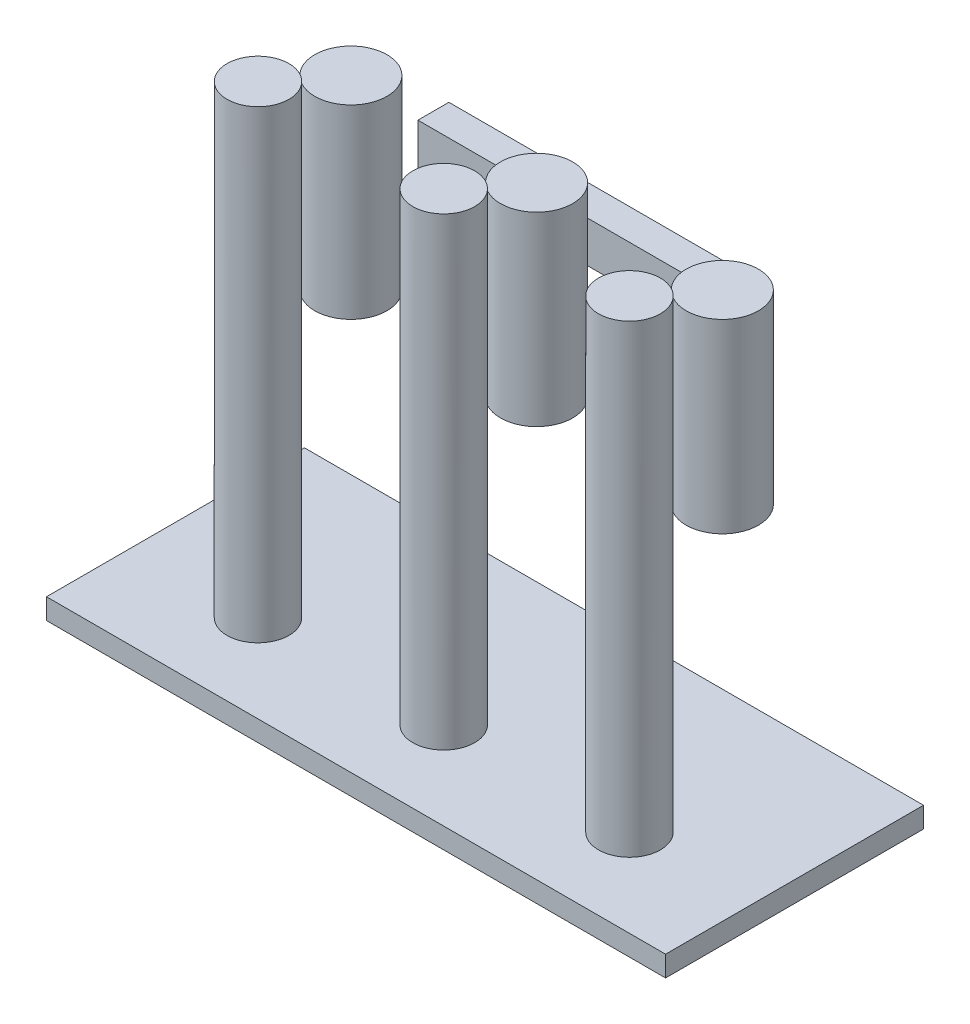
SolidWorks part; units mm, degrees
ref_plane "Front Plane" through (0, 0, 0) normal (0, 0, 1) x (1, 0, 0)
ref_plane "Top Plane" through (0, 0, 0) normal (0, 1, 0) x (1, 0, 0)
ref_plane "Right Plane" through (0, 0, 0) normal (1, 0, 0) x (0, 0, -1)
other "Configuration Table"
sketch "Sketch1" plane through (0, 0, 0) normal (0, 1, 0) x (1, 0, 0)
  line L1 (-3000, -1250) -> (3000, -1250)
  line L2 (-3000, -1250) -> (-3000, 1250)
  line L3 (-3000, 1250) -> (3000, 1250)
  line L4 (3000, -1250) -> (3000, 1250)
extrude "Boss-Extrude1" add sketch "Sketch1" along normal blind 200
sketch "Sketch2" plane through (0, 0, 0) normal (0, 1, 0) x (1, 0, 0)
  circle A0 centre (-1800, -400) radius 300
extrude "Boss-Extrude2" add sketch "Sketch2" along normal blind 4500 from offset 200
sketch "Sketch3" plane through (0, 0, 0) normal (0, 1, 0) x (1, 0, 0)
  circle A0 centre (-1800, 500) radius 350
extrude "Boss-Extrude3" add sketch "Sketch3" along normal blind 1800 from offset 2500
sketch "Sketch4" plane through (0, 0, 0) normal (0, 1, 0) x (1, 0, 0)
  circle A0 centre (0, -400) radius 300
extrude "Boss-Extrude4" add sketch "Sketch4" along normal blind 4500 from offset 200
sketch "Sketch5" plane through (0, 0, 0) normal (0, 1, 0) x (1, 0, 0)
  circle A0 centre (0, 500) radius 350
extrude "Boss-Extrude5" add sketch "Sketch5" along normal blind 1800 from offset 2500
sketch "Sketch6" plane through (0, 0, 0) normal (0, 1, 0) x (1, 0, 0)
  circle A0 centre (1800, -400) radius 300
extrude "Boss-Extrude6" add sketch "Sketch6" along normal blind 4500 from offset 200
sketch "Sketch7" plane through (0, 0, 0) normal (0, 1, 0) x (1, 0, 0)
  circle A0 centre (1800, 500) radius 350
extrude "Boss-Extrude7" add sketch "Sketch7" along normal blind 1800 from offset 2500
sketch "Sketch8" plane through (0, 0, 0) normal (0, 1, 0) x (1, 0, 0)
  line L1 (-1500, 850) -> (1500, 850)
  line L2 (-1500, 850) -> (-1500, 1150)
  line L3 (-1500, 1150) -> (1500, 1150)
  line L4 (1500, 850) -> (1500, 1150)
extrude "Boss-Extrude8" add sketch "Sketch8" along normal blind 400 from offset 3500
